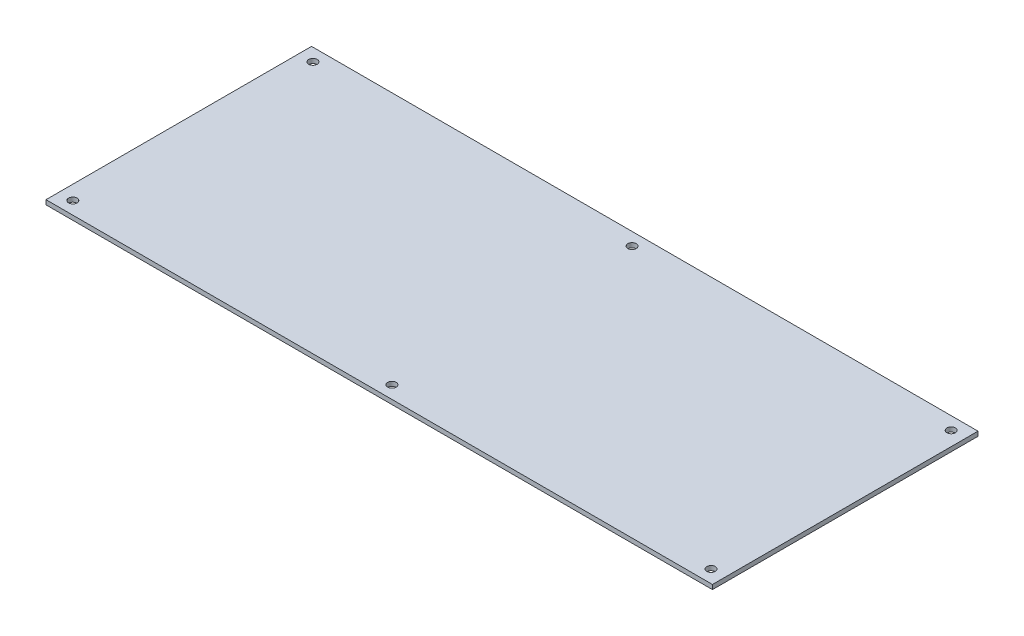
SolidWorks part; units mm, degrees
ref_plane "Front Plane" through (0, 0, 0) normal (0, 0, 1) x (1, 0, 0)
ref_plane "Top Plane" through (0, 0, 0) normal (0, 1, 0) x (1, 0, 0)
ref_plane "Right Plane" through (0, 0, 0) normal (1, 0, 0) x (0, 0, -1)
sketch "Sketch1" plane through (0, 0, 0) normal (0, 1, 0) x (1, 0, 0)
  line L1 (-235.915, -94) -> (235.915, -94)
  line L2 (-235.915, -94) -> (-235.915, 94)
  line L3 (-235.915, 94) -> (235.915, 94)
  line L4 (235.915, -94) -> (235.915, 94)
  line L5 (-235.915, -94) -> (235.915, 94) construction
  line L6 (-235.915, 94) -> (235.915, -94) construction
  point P0 (0, 0)
  dimension "D1" = 188
  dimension "D2" = 471.83
base flange "Base-Flange2" sketch "Sketch1" thickness 3.18 reverse thickness direction no parameters "D1"=0.7366
sketch "Sketch2" plane through (0, -3.18, 0) normal (0, -1, 0) x (1, 0, 0)
  line L0 (-235.915, -94) -> (-235.915, 94) construction
  line L1 (-235.915, 94) -> (235.915, 94) construction
  line L2 (-235.915, 0) -> (235.915, 0) construction
  line L3 (235.915, 94) -> (235.915, -94) construction
  line L4 (0, 94) -> (0, -94) construction
  line L5 (235.915, -94) -> (-235.915, -94) construction
  circle A0 centre (-225.915, 85) radius 3
  circle A1 centre (-225.915, -85) radius 3
  circle A2 centre (225.915, -85) radius 3
  circle A3 centre (225.915, 85) radius 3
  circle A4 centre (0, 85) radius 3
  circle A5 centre (0, -85) radius 3
  point P22 (0, 0)
  dimension "D1" = 6
  dimension "D2" = 10
  dimension "D3" = 9
extrude "Cut-Extrude1" cut sketch "Sketch2" against normal through all both and the other way through all normal cut yes
sketch "Bend-Lines3" [suppressed] plane through (0, 0, 0) normal (0, 1, 0) x (1, 0, 0)
sketch "Bounding-Box3" [suppressed] plane through (0, 0, 0) normal (0, 1, 0) x (1, 0, 0)
sheet metal parameters "Sheet-Metal2" thickness 3.18 parameters "D1"=0.7366
flat pattern "Flat-Pattern2" [suppressed]
sketch "Bend-Lines4" plane through (0, 0, 0) normal (0, 1, 0) x (1, 0, 0)
sketch3d "Bounding-Box4" [suppressed]
  line L0 (235.915, 94, 0) -> (-235.915, 94, 0) construction
  line L1 (235.915, -94, 0) -> (-235.915, -94, 0) construction
  line L2 (235.915, 94, 0) -> (235.915, -94, 0) construction
  line L3 (-235.915, 94, 0) -> (-235.915, -94, 0) construction
sheet metal parameters "Sheet-Metal3" thickness 3.18 parameters "D1"=0.7366
flat pattern "Flat-Pattern2"
sketch "Bend-Lines4" plane through (0, 0, 0) normal (0, 1, 0) x (1, 0, 0)
sketch3d "Bounding-Box4" [suppressed]
  line L0 (235.915, 94, 0) -> (-235.915, 94, 0) construction
  line L1 (235.915, -94, 0) -> (-235.915, -94, 0) construction
  line L2 (235.915, 94, 0) -> (235.915, -94, 0) construction
  line L3 (-235.915, 94, 0) -> (-235.915, -94, 0) construction
